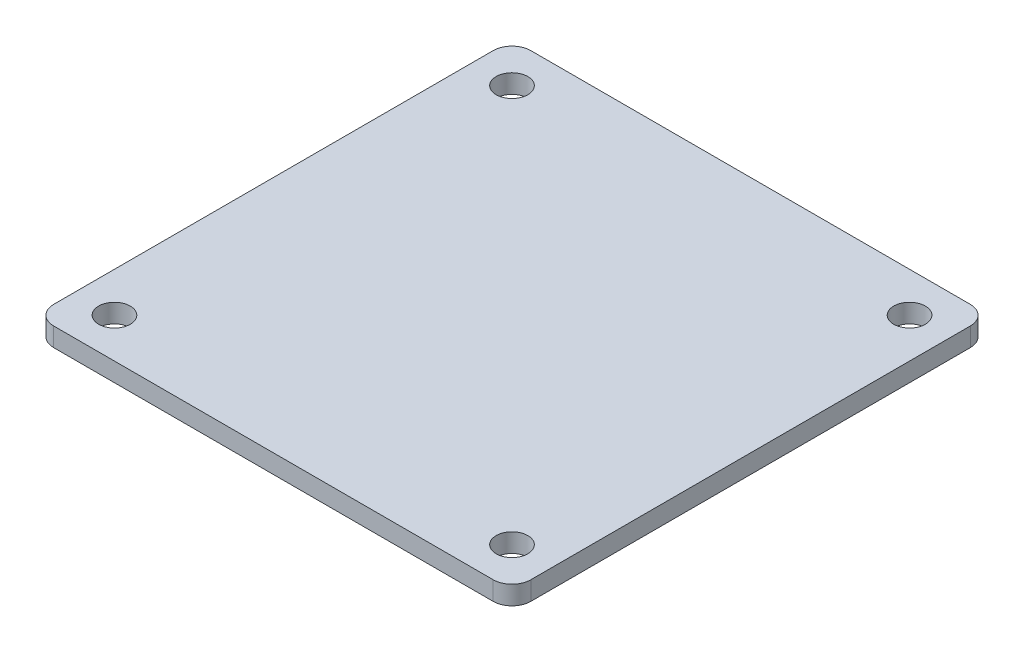
SolidWorks part; units mm, degrees
ref_plane "Front Plane" through (0, 0, 0) normal (0, 0, 1) x (1, 0, 0)
ref_plane "Top Plane" through (0, 0, 0) normal (0, 1, 0) x (1, 0, 0)
ref_plane "Right Plane" through (0, 0, 0) normal (1, 0, 0) x (0, 0, -1)
sketch "Sketch1" plane through (0, 0, 0) normal (0, 1, 0) x (1, 0, 0)
  line L1 (-38.1, -38.1) -> (38.1, -38.1)
  line L2 (-38.1, -38.1) -> (-38.1, 38.1)
  line L3 (-38.1, 38.1) -> (38.1, 38.1)
  line L4 (38.1, -38.1) -> (38.1, 38.1)
  line L5 (-38.1, -38.1) -> (38.1, 38.1) construction
  line L6 (-38.1, 38.1) -> (38.1, -38.1) construction
  circle A0 centre (-31.75, 31.75) radius 2.525
  circle A1 centre (31.75, 31.75) radius 2.525
  circle A2 centre (31.75, -31.75) radius 2.525
  circle A3 centre (-31.75, -31.75) radius 2.525
  point P0 (0, 0)
  point P8 (-21.5328, -21.5328)
  point P9 (0, 0)
  point P11 (0, 0)
  point P14 (0, 0)
  point P17 (0, 0)
  point P20 (0, 0)
  dimension "D3" = 6.35
  dimension "D4" = 5.05
  dimension "D1" = 76.2
  dimension "D2" = 76.2
  dimension "D5" = 4
extrude "Boss-Extrude1" add sketch "Sketch1" along normal blind 3
fillet "Fillet1" radius 3 4 edges at (38.1, 1.5, 38.1) (38.1, 1.5, -38.1) (-38.1, 1.5, -38.1) (-38.1, 1.5, 38.1)
